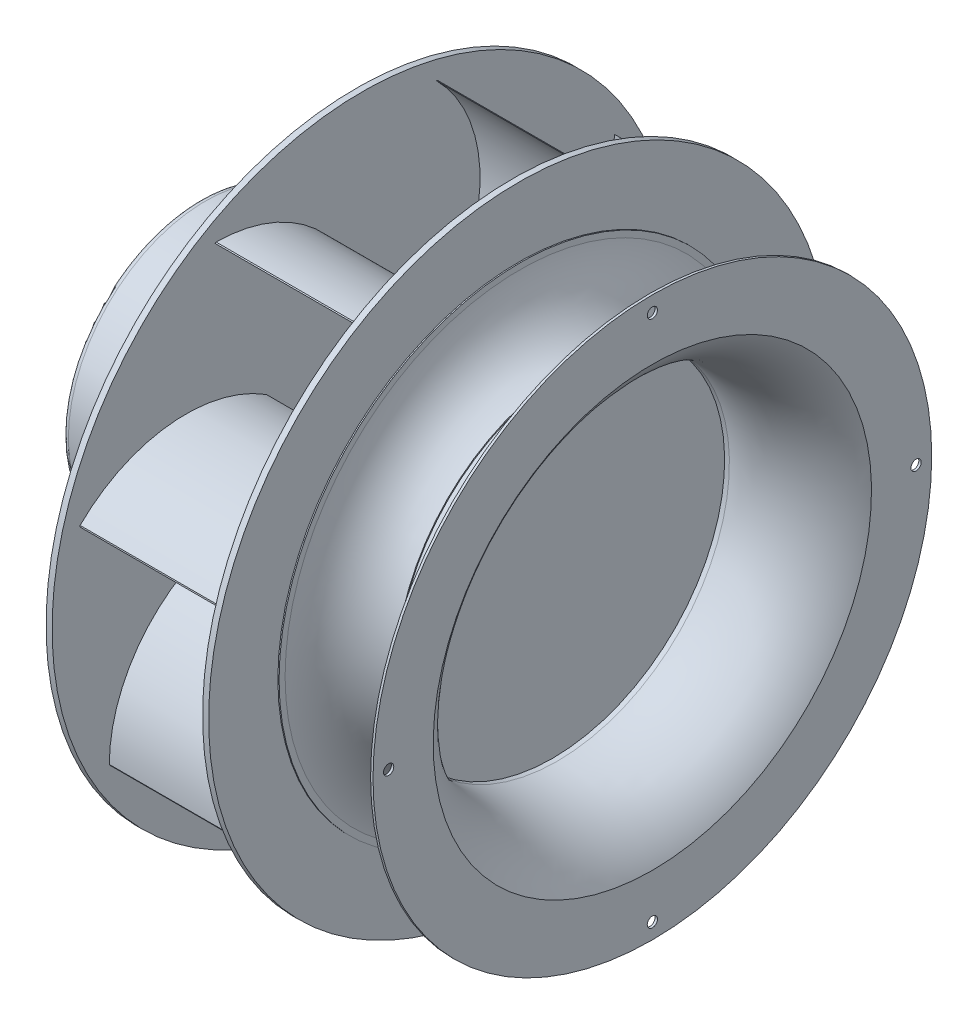
SolidWorks part; units mm, degrees
ref_plane "Front Plane" through (0, 0, 0) normal (0, 0, 1) x (1, 0, 0)
ref_plane "Top Plane" through (0, 0, 0) normal (0, 1, 0) x (1, 0, 0)
ref_plane "Right Plane" through (0, 0, 0) normal (1, 0, 0) x (0, 0, -1)
sketch "Sketch1" plane through (0, 0, 0) normal (0, 0, 1) x (1, 0, 0)
  line L0 (0, 0) -> (831.9083, 0) construction
  line L1 (0, 0) -> (0, 109)
  line L2 (5, 114) -> (70, 114)
  line L3 (70, 114) -> (70, 138)
  line L4 (70, 138) -> (90, 138)
  line L5 (90, 138) -> (90, 98)
  line L6 (90, 98) -> (95, 98)
  line L7 (95, 98) -> (95, 133)
  line L8 (95, 133) -> (105, 133)
  line L9 (105, 133) -> (105, 98)
  line L10 (105, 98) -> (130, 98)
  line L11 (130, 98) -> (130, 0)
  line L12 (130, 0) -> (0, 0)
  arc A0 (5, 114) -> (0, 109) centre (5, 109) ccw
  point P16 (0, 114)
  dimension "D10" = 5
  dimension "D1" = 114
  dimension "D2" = 24
  dimension "D3" = 70
  dimension "D4" = 40
  dimension "D5" = 35
  dimension "D6" = 5
  dimension "D7" = 20
  dimension "D8" = 10
  dimension "D9" = 60
revolve "Revolve1" add sketch "Sketch1" angle 360 about L0
sketch "Sketch2" plane through (130, 0, 0) normal (1, 0, 0) x (0, 0, -1)
  circle A0 centre (0, 0) radius 257.5
  dimension "D1" = 515
extrude "Extrude1" add sketch "Sketch2" along normal blind 5
sketch "Sketch9" plane through (130, 0, 0) normal (-1, 0, 0) x (0, 0, 1)
  circle A0 centre (0, 0) radius 252.5
  circle A1 centre (0, 0) radius 100
  circle A2 centre (0, 0) radius 257.5 construction
  dimension "D1" = 5
  dimension "D2" = 200
extrude "Extrude7" cut sketch "Sketch9" against normal blind 3
ref_plane "Plane1" through (260, 0, 0) normal (1, 0, 0) x (0, 0, -1)
sketch "Sketch3" plane through (260, 0, 0) normal (1, 0, 0) x (0, 0, -1)
  circle A0 centre (0, 0) radius 257.5
  dimension "D1" = 515
extrude "Extrude2" add sketch "Sketch3" along normal blind 5 separate body
sketch "Sketch4" plane through (135, 0, 0) normal (1, 0, 0) x (0, 0, -1)
  line L0 (0, 0) -> (0, 242.5) construction
  line L1 (0, 0) -> (128.75, 223.0015) construction
  line L2 (0, 112.5) -> (0.866, 112) construction
  line L3 (121.25, 210.0112) -> (122.116, 209.5112) construction
  line L4 (-121.25, 210.0112) -> (-122.116, 209.5112)
  line L5 (0, 112.5) -> (-0.866, 112)
  circle A0 centre (0, 0) radius 242.5 construction
  circle A1 centre (0, 0) radius 257.5 construction
  circle A2 centre (0, 0) radius 112.5 construction
  arc A3 (0, 112.5) -> (121.25, 210.0112) centre (121.9404, 85.0131) cw construction
  arc A4 (0.866, 112) -> (122.116, 209.5112) centre (122.8065, 84.5131) cw construction
  arc A5 (0, 112.5) -> (-121.25, 210.0112) centre (-121.9404, 85.0131) ccw
  arc A6 (-0.866, 112) -> (-122.116, 209.5112) centre (-122.8065, 84.5131) ccw
  dimension "D1" = 15
  dimension "D2" = 225
  dimension "D6" = 125
  dimension "D7" = 125
  dimension "D3" = 30
  dimension "D4" = 60
  dimension "D5" = 1
extrude "Extrude3" add sketch "Sketch4" along normal up to surface (130 mm away) up to face at (265, 0, -257.5)
ref_axis "Axis1" through (253.5503, 0, 0) along (-1, 0, 0)
pattern_circular "CirPattern1" count 8 over 360 about axis through (253.5503, 0, 0) along (-1, 0, 0) of "Extrude3"
sketch "Sketch5" plane through (0, 0, 0) normal (0, 0, 1) x (1, 0, 0)
  line L0 (0, 0) -> (527.2916, 0) construction
  line L1 (253.5503, 0) -> (75.411, 0) construction
  line L2 (265, 200) -> (266, 200)
  line L3 (266, 200) -> (266, 195)
  line L4 (265, 200) -> (265, 195)
  line L5 (309, 146) -> (309, 145)
  line L6 (70, 138) -> (70, -138) construction
  line L7 (265, -257.5) -> (265, 257.5) construction
  arc A0 (266, 195) -> (309, 146) centre (325.3621, 203.7259) ccw
  arc A1 (265, 195) -> (309, 145) centre (324.4681, 202.9719) ccw
  dimension "D7" = 60
  dimension "D8" = 60
  dimension "D1" = 145
  dimension "D2" = 1
  dimension "D3" = 1
  dimension "D4" = 5
  dimension "D5" = 200
  dimension "D6" = 239
revolve "Revolve2" add sketch "Sketch5" angle 360 about L0
ref_plane "Plane3" through (376, 0, 0) normal (1, 0, 0) x (0, 0, -1)
sketch "Sketch6" plane through (0, 0, 0) normal (0, 0, 1) x (1, 0, 0)
  line L0 (376, 232) -> (374, 232)
  line L1 (376, -251.35) -> (376, 251.35) construction
  line L2 (374, 232) -> (374, 182)
  line L3 (0, 0) -> (615.1417, 0) construction
  line L4 (0, 114) -> (0, -114) construction
  line L5 (253.5503, 0) -> (75.411, 0) construction
  line L6 (376, 232) -> (376, 182)
  line L7 (293, 145) -> (297, 145)
  line L8 (293, 145) -> (293, 143)
  line L9 (293, 143) -> (297, 143)
  arc A0 (297, 145) -> (374, 182) centre (306.2033, 224.4689) ccw
  arc A1 (297, 143) -> (376, 182) centre (306.9389, 222.3802) ccw
  dimension "D7" = 80
  dimension "D8" = 80
  dimension "D1" = 232
  dimension "D2" = 2
  dimension "D3" = 182
  dimension "D4" = 83
  dimension "D5" = 145
  dimension "D6" = 4
revolve "Revolve3" add sketch "Sketch6" angle 360 about L3
sketch "Sketch7" plane through (376, 0, 0) normal (1, 0, 0) x (0, 0, -1)
  line L0 (0, 0) -> (0, 219) construction
  circle A0 centre (0, 0) radius 219 construction
  circle A1 centre (0, 219) radius 4.25
  dimension "D1" = 438
  dimension "D2" = 8.5
extrude "Extrude5" cut sketch "Sketch7" against normal blind 5
pattern_circular "CirPattern2" count 4 over 360 about axis through (253.5503, 0, 0) along (-1, 0, 0) of "Extrude5"
sketch "Sketch8" plane through (0, 0, 0) normal (1, 0, 0) x (0, 0, -1)
  line L0 (0, 0) -> (0, 126) construction
  circle A0 centre (0, 0) radius 126 construction
  circle A1 centre (0, 126) radius 5
  dimension "D1" = 252
  dimension "D2" = 10
extrude "Extrude6" cut sketch "Sketch8" along normal up to surface (90 mm away) up to face at (90, 0, 138)
pattern_circular "CirPattern3" count 8 over 360 about axis through (253.5503, 0, 0) along (-1, 0, 0) of "Extrude6"
